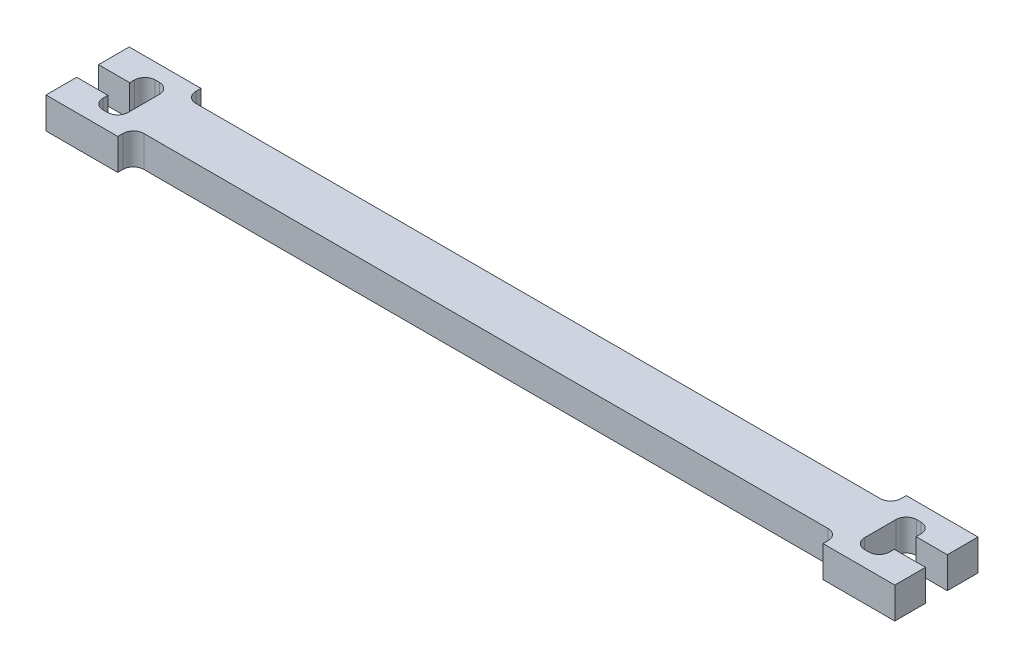
SolidWorks part; units mm, degrees
ref_plane "Front Plane" through (0, 0, 0) normal (0, 0, 1) x (1, 0, 0)
ref_plane "Top Plane" through (0, 0, 0) normal (0, 1, 0) x (1, 0, 0)
ref_plane "Right Plane" through (0, 0, 0) normal (1, 0, 0) x (0, 0, -1)
sketch "Sketch1" plane through (0, 0, 0) normal (0, 1, 0) x (1, 0, 0)
  line L0 (-40.8, 0) -> (40.8, 0) construction
  line L1 (-40.8, 4) -> (40.8, 4)
  line L2 (-40.8, 4) -> (-40.8, -4)
  line L3 (-40.8, -4) -> (40.8, -4)
  line L4 (40.8, 4) -> (40.8, -4)
  line L5 (-40.8, 4) -> (40.8, -4) construction
  line L6 (-40.8, -4) -> (40.8, 4) construction
  line L7 (-35.4, 2.5) -> (-35.4, 4) construction
  line L8 (-40.8, 1.05) -> (-37.8, 1.05)
  line L9 (-40.8, 1.05) -> (-40.8, -1.05)
  line L10 (-40.8, -1.05) -> (-37.8, -1.05)
  line L11 (-37.8, 1.05) -> (-37.8, -1.05)
  line L12 (-40.8, 1.05) -> (-37.8, -1.05) construction
  line L13 (-40.8, -1.05) -> (-37.8, 1.05) construction
  line L14 (-37.8, 2.5) -> (-35.4, 2.5)
  line L15 (-37.8, 2.5) -> (-37.8, -2.5)
  line L16 (-37.8, -2.5) -> (-35.4, -2.5)
  line L17 (-35.4, 2.5) -> (-35.4, -2.5)
  line L18 (-37.8, 2.5) -> (-35.4, -2.5) construction
  line L19 (-37.8, -2.5) -> (-35.4, 2.5) construction
  line L20 (-33.9, 2.5) -> (33.9, 2.5)
  line L21 (-33.9, 2.5) -> (-33.9, -2.5)
  line L22 (-33.9, -2.5) -> (33.9, -2.5)
  line L23 (33.9, 2.5) -> (33.9, -2.5)
  line L24 (-33.9, 2.5) -> (33.9, -2.5) construction
  line L25 (-33.9, -2.5) -> (33.9, 2.5) construction
  line L26 (-35.4, 2.5) -> (-33.9, 2.5) construction
  line L27 (-33.9, 2.5) -> (-33.9, 4)
  line L28 (-33.9, -2.5) -> (-33.9, -4)
  line L29 (0, 4) -> (0, -4) construction
  line L30 (33.9, -2.5) -> (33.9, -4)
  line L31 (-40.8, 4) -> (-40.8, -4)
  line L32 (40.8, 4) -> (40.8, -4)
  line L33 (33.9, 2.5) -> (33.9, 4)
  line L34 (40.8, -1.05) -> (37.8, -1.05)
  line L35 (37.8, -2.5) -> (35.4, -2.5)
  line L36 (35.4, 2.5) -> (35.4, -2.5)
  line L37 (37.8, 2.5) -> (35.4, 2.5)
  line L38 (37.8, 2.5) -> (37.8, -2.5)
  line L39 (40.8, 1.05) -> (37.8, 1.05)
  point P0 (0, 0)
  point P8 (-39.3, 0)
  point P13 (-36.6, 0)
  point P18 (0, 0)
  dimension "D1" = 8
  dimension "D2" = 81.6
  dimension "D3" = 3
  dimension "D4" = 2.4
  dimension "D5" = 5
  dimension "D6" = 2.1
extrude "Base shape" add sketch "Sketch1" along normal blind 3 contours L23 L20 L21 L22 | L28 L21 L27 L1 L2 L8 L15 L14 L17 L16 L10 L3 | L39 L4 L1 L33 L23 L30 L3 L32 L34 L38 L35 L36 L37 region at (-37.35, 0, -3.8944) region at (37.35, 0, -3.8944) region at (0, 0, 0)
fillet "Milling fillets" radius 1 12 edges at (37.8, 1.5, 2.5) (-35.4, 1.5, 2.5) (-37.8, 1.5, 2.5) (35.4, 1.5, 2.5) (35.4, 1.5, -2.5) (-37.8, 1.5, -2.5) (-35.4, 1.5, -2.5) (37.8, 1.5, -2.5) (33.9, 1.5, 2.5) (33.9, 1.5, -2.5) (-33.9, 1.5, -2.5) (-33.9, 1.5, 2.5)
sketch "Center axis sketch" plane through (40.8, 0, 0) normal (1, 0, 0) x (0, 0, -1)
  line L0 (-1.05, 0) -> (1.05, 3) construction
  point P4 (0, 1.5)
ref_axis "Center axis" through (-46.4653, 1.5, 0) along (1, 0, 0)
